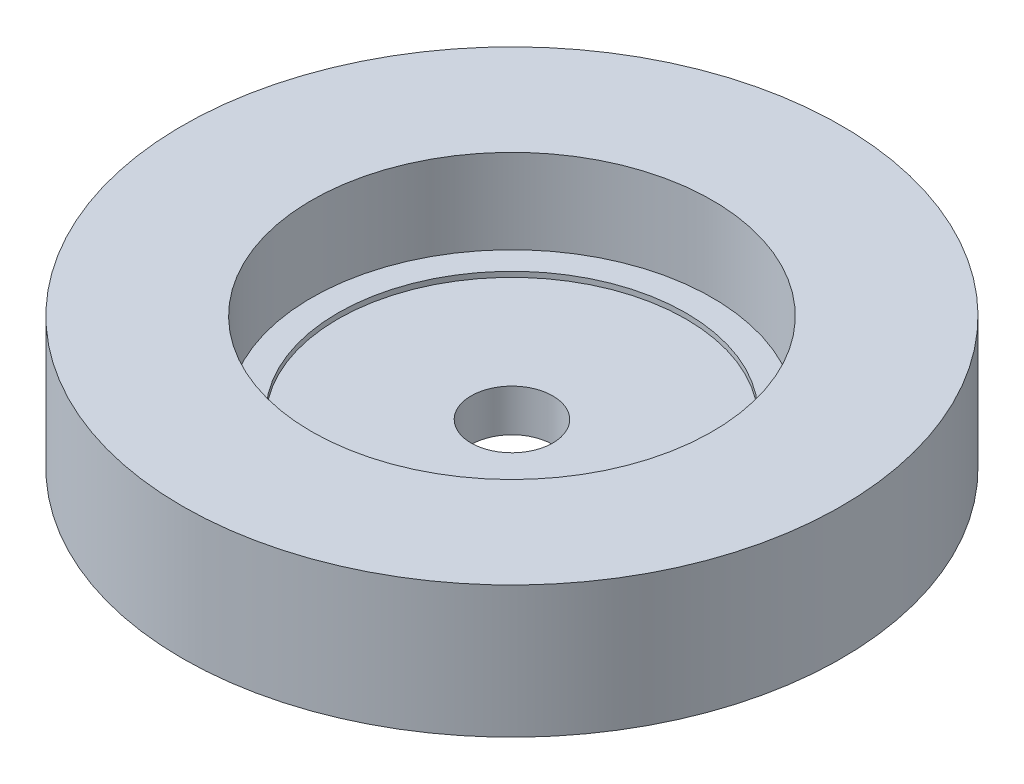
SolidWorks part; units mm, degrees
ref_plane "正面" through (0, 0, 0) normal (0, 0, 1) x (1, 0, 0)
ref_plane "平面" through (0, 0, 0) normal (0, 1, 0) x (1, 0, 0)
ref_plane "右側面" through (0, 0, 0) normal (1, 0, 0) x (0, 0, -1)
sketch "ｽｹｯﾁ1" plane through (0, 0, 0) normal (0, 1, 0) x (1, 0, 0)
  circle A0 centre (0, 0) radius 7.6
  circle A1 centre (0, 0) radius 12.5
  dimension "D1" = 15.2
  dimension "D2" = 25
extrude "ﾎﾞｽ - 押し出し1" add sketch "ｽｹｯﾁ1" along normal blind 5
sketch "ｽｹｯﾁ2" plane through (0, 0, 0) normal (0, -1, 0) x (1, 0, 0)
  circle A0 centre (0, 0) radius 7.6
  circle A1 centre (0, 0) radius 7.6 construction
  circle A2 centre (0, 0) radius 1.55
  dimension "D1" = 3.1
extrude "ﾎﾞｽ - 押し出し2" add sketch "ｽｹｯﾁ2" against normal blind 1.6
sketch "ｽｹｯﾁ3" plane through (0, 1.6, 0) normal (0, 1, 0) x (1, 0, 0)
  circle A0 centre (0, 0) radius 7.6
  circle A1 centre (0, 0) radius 6.6
  circle A2 centre (0, 0) radius 7.6 construction
  dimension "D1" = 1
extrude "ﾎﾞｽ - 押し出し3" add sketch "ｽｹｯﾁ3" along normal blind 0.2
